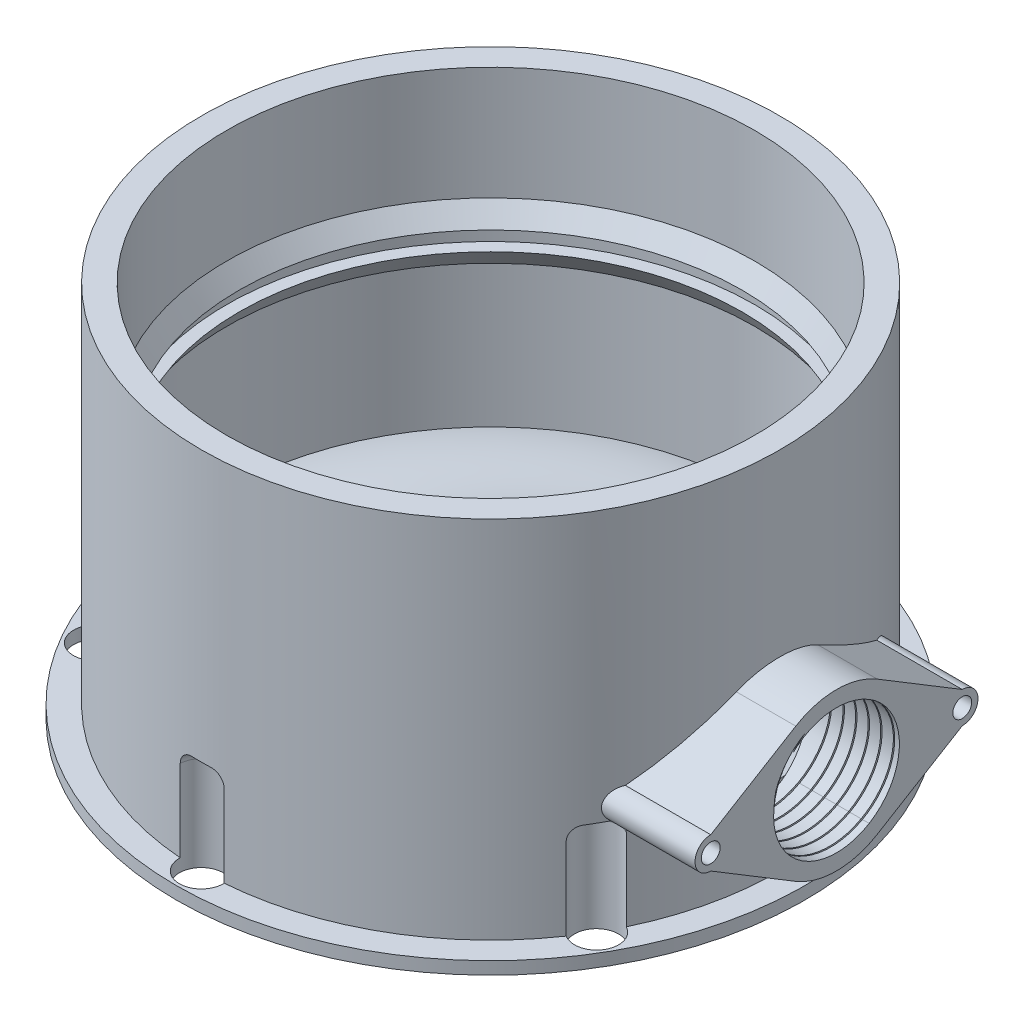
SolidWorks part; units mm, degrees
ref_plane "Front Plane" through (0, 0, 0) normal (0, 0, 1) x (1, 0, 0)
ref_plane "Top Plane" through (0, 0, 0) normal (0, 1, 0) x (1, 0, 0)
ref_plane "Right Plane" through (0, 0, 0) normal (1, 0, 0) x (0, 0, -1)
sketch "Sketch4" plane through (0, 0, 0) normal (0, 1, 0) x (1, 0, 0)
  circle A0 centre (0, 0) radius 53.34
  circle A1 centre (0, 0) radius 63.5
  dimension "D1" = 106.68
  dimension "D2" = 127
extrude "Boss-Extrude1" add sketch "Sketch4" along normal blind 2.54
sketch "Sketch6" plane through (0, 2.54, 0) normal (0, 1, 0) x (1, 0, 0)
  line L0 (0, -53.34) -> (0, -63.5) construction
  circle A0 centre (0, 0) radius 53.34 construction
  circle A1 centre (0, 0) radius 63.5 construction
  circle A2 centre (0, -58.42) radius 4.445
  dimension "D1" = 8.89
extrude "Cut-Extrude2" cut sketch "Sketch6" against normal blind 2.54
pattern_circular "CirPattern1" count 6 over 360 about axis through (0, 2.54, 0) along (0, 1, 0) of "Cut-Extrude2"
sketch "Sketch9" plane through (0, 2.54, 0) normal (0, 1, 0) x (1, 0, 0)
  circle A0 centre (0, 0) radius 58.42
  circle A1 centre (0, 0) radius 53.34
  dimension "D1" = 106.68
extrude "Boss-Extrude2" add sketch "Sketch9" along normal blind 73.66
extrude "Cut-Extrude3" cut sketch "Sketch6<2>" along normal blind 19.05
sketch "Sketch6<2>" plane through (0, 2.54, 0) normal (0, 1, 0) x (1, 0, 0) same geometry as "Sketch6"
fillet "Fillet1" radius 2.54 1 edges at (0, 21.59, 53.975)
pattern_circular "CirPattern3" count 6 over 360 about axis through (0, 76.2, 0) along (0, -1, 0) of "Fillet1", "Cut-Extrude3"
ref_plane "Plane7" through (69.85, 0, 0) normal (1, 0, 0) x (0, 0, -1)
sketch "Sketch10" plane through (69.85, 0, 0) normal (1, 0, 0) x (0, 0, -1)
  line L1 (-25.4, 27.305) -> (-8.2246, 37.7084)
  line L2 (-25.4, 20.955) -> (-8.2246, 10.5516)
  line L3 (0, 0) -> (0, 77.5888) construction
  line L4 (25.4, 27.305) -> (8.2246, 37.7084)
  line L5 (25.4, 20.955) -> (8.2246, 10.5516)
  line L8 (25.2788, 2.54) -> (-25.2788, 2.54) construction
  line L9 (63.5, 2.54) -> (-63.5, 2.54) construction
  arc A0 (-8.2246, 10.5516) -> (8.2246, 10.5516) centre (0, 24.13) ccw
  arc A1 (-25.4, 27.305) -> (-25.4, 20.955) centre (-25.4, 24.13) ccw
  arc A2 (25.4, 20.955) -> (25.4, 27.305) centre (25.4, 24.13) ccw
  circle A3 centre (0, 24.13) radius 12.7
  circle A4 centre (-25.4, 24.13) radius 1.905
  circle A5 centre (25.4, 24.13) radius 1.905
  arc A6 (8.2246, 37.7084) -> (-8.2246, 37.7084) centre (0, 24.13) ccw
  point P4 (0, 8.255)
  dimension "D1" = 31.75
  dimension "D2" = 6.35
  dimension "D3" = 6.35
  dimension "D4" = 25.4
  dimension "D6" = 25.4
  dimension "D7" = 3.81
  dimension "D8" = 3.81
  dimension "D9" = 21.59
  dimension "D5" = 25.4
  dimension "D10" = 5.715
extrude "Boss-Extrude3" add sketch "Sketch10" against normal up to surface (12.8271 mm away) up to face at (0, 76.2, 58.42)
sketch "Sketch11" plane through (69.85, 0, 0) normal (1, 0, 0) x (0, 0, -1)
  circle A0 centre (0, 24.13) radius 12.7
extrude "Cut-Extrude5" cut sketch "Sketch11" against normal up to surface (18.044 mm away) up to face at (0, 0, 53.34)
sketch "Sketch12" plane through (69.85, 0, 0) normal (1, 0, 0) x (0, 0, -1)
  circle A0 centre (0, 24.13) radius 12.7
curve "Helix/Spiral1" pitch 2.54 height 15.24 radius 12.7 centre (69.85, 24.13, 0) axis (-1, 0, 0) start towards (0, 0.7071, 0.7071)
ref_plane "Plane8" through (69.85, 33.1103, 8.9803) normal (-0.0318, 0.7067, -0.7067) x (0.9523, -0.1933, -0.2361)
sketch "Sketch13" plane through (69.85, 33.1103, 8.9803) normal (-0.0318, 0.7067, -0.7067) x (0.9523, -0.1933, -0.2361)
  line L1 (0, 0.381) -> (-0.254, 0.1905)
  line L2 (-0.254, 0.1905) -> (-0.254, -0.1905)
  line L3 (-0.254, -0.1905) -> (0, -0.381)
  line L4 (0, 0) -> (-0.254, 0) construction
  line L5 (0, 0.381) -> (0, -0.381)
  point P7 (0, 0)
  point P12 (-0.254, 0)
  dimension "D1" = 0.381
  dimension "D2" = 0.762
  dimension "D3" = 0.254
sweep "Cut-Sweep1" cut profiles "Sketch13" path "Helix/Spiral1" align with end faces yes
sketch "Sketch14" plane through (0, 0, 0) normal (0, 0, 1) x (1, 0, 0)
  line L0 (0, 0) -> (0, 31.75) construction
  line L1 (-53.34, 0) -> (53.34, 0) construction
  line L2 (0, 76.2) -> (0, 21.59) construction
  line L3 (6.35, 31.75) -> (6.35, 7.5944)
  line L4 (53.34, 13.2796) -> (53.34, 0) construction
  line L5 (6.35, 7.5944) -> (53.34, 7.5944)
  line L6 (53.34, 7.5944) -> (53.34, 13.2796)
  line L11 (50.8, 45.72) -> (53.34, 45.72)
  line L12 (53.34, 45.72) -> (53.34, 41.91)
  line L13 (53.34, 49.53) -> (50.8, 49.53)
  line L16 (53.34, 53.34) -> (53.34, 49.53)
  line L17 (50.8, 45.72) -> (53.34, 41.91)
  line L18 (53.34, 53.34) -> (50.8, 49.53)
  spline S1 degree 3 poles (6.35, 31.75) (9.8008, 26.6975) (17.151, 19.9797) (34.0829, 14.6451) (45.6422, 15.3114) (53.34, 13.2796) knots 0 0 0 0 0.349551 0.548128 1 1 1 1
  point P23 (52.07, 49.53)
  dimension "D2" = 6.35
  dimension "D4" = 3.81
  dimension "D3" = 53.34
  dimension "D1" = 31.75
  dimension "D5" = 53.34
  dimension "D6" = 3.81
revolve "Revolve1" add sketch "Sketch14" angle 360 about L0
